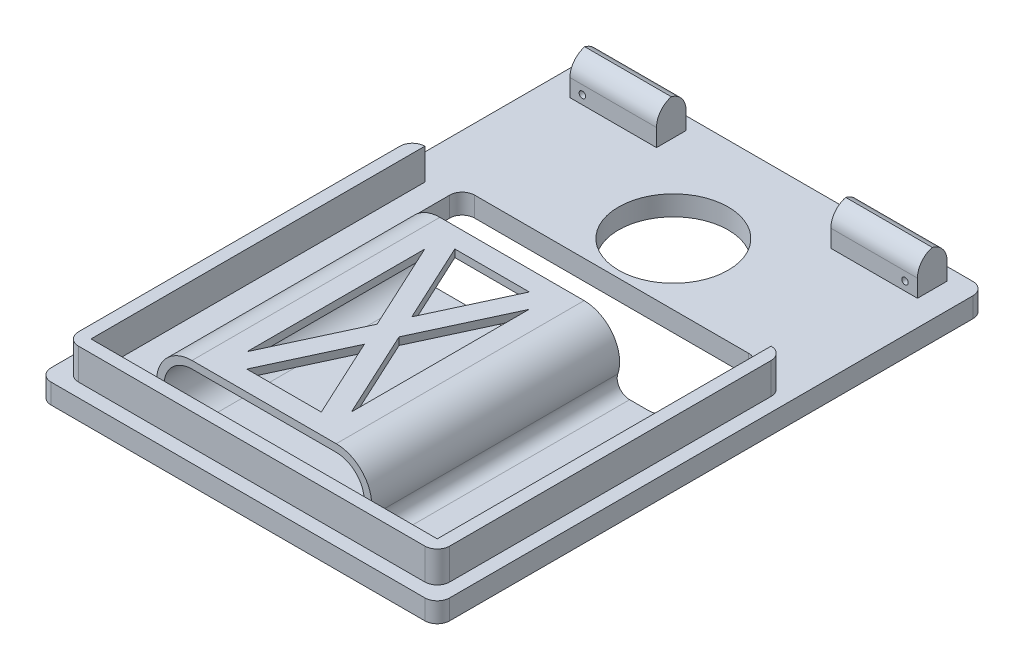
SolidWorks part; units mm, degrees
ref_plane "Front Plane" through (0, 0, 0) normal (0, 0, 1) x (1, 0, 0)
ref_plane "Top Plane" through (0, 0, 0) normal (0, 1, 0) x (1, 0, 0)
ref_plane "Right Plane" through (0, 0, 0) normal (1, 0, 0) x (0, 0, -1)
sketch "Sketch3" plane through (0, 0, 0) normal (0, 1, 0) x (1, 0, 0)
  line L0 (-75, 110) -> (75, 110)
  line L1 (-75, -105) -> (75, -105)
  line L2 (-75, -105) -> (-75, 105)
  line L4 (75, -105) -> (75, 105)
  line L5 (-75, -105) -> (75, 105) construction
  line L6 (-75, 105) -> (75, -105) construction
  line L7 (80, -105) -> (80, 105)
  line L8 (-75, -110) -> (75, -110)
  line L9 (-80, -105) -> (-80, 105)
  line L10 (-80, -110) -> (80, -110) construction
  line L11 (-80, -110) -> (-80, 110) construction
  line L12 (80, -110) -> (80, 110) construction
  line L13 (-80, 110) -> (80, 110) construction
  line L15 (-75, 105) -> (75, 105)
  line L19 (-75, 105) -> (75, 105) construction
  line L20 (-69.75, 104.9) -> (69.75, 104.9)
  line L21 (-69.75, 104.9) -> (-69.75, 93)
  line L22 (-69.75, 93) -> (69.75, 93)
  line L23 (69.75, 104.9) -> (69.75, 93)
  arc A0 (-75, -110) -> (-80, -105) centre (-75, -105) cw
  arc A1 (80, -105) -> (75, -110) centre (75, -105) cw
  arc A2 (75, 110) -> (80, 105) centre (75, 105) cw
  arc A3 (-75, 110) -> (-80, 105) centre (-75, 105) ccw
  point P0 (0, 0)
  point P5 (0, 93)
  dimension "D4" = 5
  dimension "D1" = 75
  dimension "D2" = 210
  dimension "D5" = 11.9
  dimension "D6" = 139.5
  dimension "D7" = 0.1
  dimension "D3" = 5
extrude "Boss-Extrude1" add sketch "Sketch3" along normal blind 8 contours L1 L4 L2 | L0 A3 L9 A0 L8 A1 L7 A2 L4 L1 L2 | L2 L4 | L23 L15 L21 L22 region at (0, 0, -107.2797) region at (0, 0, 5.5048) region at (0, 0, -98.95)
extrude "Boss-Extrude2" add sketch "Sketch3<7>" along normal blind 15 from surface contours L23 L15 L21 L22 region at (0, 0, -98.95) starting at face at (0, 8, 0)
sketch "Sketch3<7>" plane through (0, 0, 0) normal (0, 1, 0) x (1, 0, 0) same geometry as "Sketch3"
fillet "Fillet1" radius 8 2 edges at (0, 23, -93) (0, 23, -104.9)
sketch "Sketch4" plane through (0, 0, 0) normal (0, -1, 0) x (1, 0, 0)
  line L1 (-55, 0) -> (55, 0)
  line L2 (-60, -5) -> (-60, -35)
  line L3 (-55, -40) -> (55, -40)
  line L4 (60, -5) -> (60, -35)
  line L5 (-75, 110) -> (75, 110) construction
  line L6 (80, 105) -> (80, -105) construction
  line L7 (-75, -110) -> (75, -110) construction
  arc A0 (-55, 0) -> (-60, -5) centre (-55, -5) ccw
  arc A1 (-60, -35) -> (-55, -40) centre (-55, -35) ccw
  arc A2 (55, -40) -> (60, -35) centre (55, -35) ccw
  arc A3 (55, 0) -> (60, -5) centre (55, -5) cw
  point P4 (0, -40)
  dimension "D4" = 5
  dimension "D1" = 70
  dimension "D2" = 110
  dimension "D3" = 20
extrude "Cut-Extrude1" cut sketch "Sketch4" against normal up to next
sketch "Sketch5" plane through (0, 8, 0) normal (0, 1, 0) x (1, 0, 0)
  line L0 (75, -105) -> (75, 105) construction
  line L1 (-75, -105) -> (75, -105) construction
  line L2 (-75, -105) -> (-75, 105) construction
  line L3 (-75, 105) -> (75, 105) construction
  line L4 (75, 110) -> (-75, 110)
  line L5 (80, -105) -> (80, 105)
  line L6 (-75, -110) -> (75, -110)
  line L7 (-80, 105) -> (-80, -105)
  line L8 (75, 110) -> (-75, 110)
  line L9 (80, -105) -> (80, 105)
  line L10 (-75, -110) -> (75, -110)
  line L11 (-80, 105) -> (-80, -105)
  line L12 (69.75, 104.9) -> (-69.75, 104.9)
  line L13 (-69.75, 104.9) -> (-69.75, 93)
  line L14 (-69.75, 93) -> (69.75, 93)
  line L15 (69.75, 93) -> (69.75, 104.9)
  line L16 (69.75, 104.9) -> (-69.75, 104.9)
  line L17 (-69.75, 104.9) -> (-69.75, 93)
  line L18 (-69.75, 93) -> (69.75, 93)
  line L19 (69.75, 93) -> (69.75, 104.9)
  line L20 (75, -105) -> (75, 105)
  line L21 (-75, -105) -> (75, -105)
  line L22 (-75, -105) -> (-75, 105)
  line L23 (-75, 105) -> (75, 105)
  line L24 (-75, 35) -> (75, 35)
  line L25 (-69.5, 34.5) -> (-69.5, -99.5)
  line L26 (-69.5, -104.5) -> (69.5, -104.5)
  line L27 (-74.5, -99.5) -> (-74.5, 29.5)
  line L28 (-69.5, 34.5) -> (69.5, 34.5)
  line L29 (74.5, -99.5) -> (74.5, 29.5)
  line L30 (-69.5, -99.5) -> (69.5, -99.5)
  line L31 (69.5, -99.5) -> (69.5, 34.5)
  arc A0 (-74.5, 29.5) -> (-69.5, 34.5) centre (-69.5, 29.5) cw
  arc A1 (69.5, 34.5) -> (74.5, 29.5) centre (69.5, 29.5) cw
  arc A2 (69.5, -104.5) -> (74.5, -99.5) centre (69.5, -99.5) ccw
  arc A3 (-69.5, -104.5) -> (-74.5, -99.5) centre (-69.5, -99.5) cw
  arc A4 (80, 105) -> (75, 110) centre (75, 105) ccw
  arc A5 (75, -110) -> (80, -105) centre (75, -105) ccw
  arc A6 (-80, -105) -> (-75, -110) centre (-75, -105) ccw
  arc A7 (-75, 110) -> (-80, 105) centre (-75, 105) ccw
  arc A8 (80, 105) -> (75, 110) centre (75, 105) ccw
  arc A9 (75, -110) -> (80, -105) centre (75, -105) ccw
  arc A10 (-80, -105) -> (-75, -110) centre (-75, -105) ccw
  arc A11 (-75, 110) -> (-80, 105) centre (-75, 105) ccw
  point P26 (0, -104.5)
  point P42 (0, -99.5)
  dimension "D7" = 5
  dimension "D3" = 75
  dimension "D4" = 0.5
  dimension "D5" = 0.5
  dimension "D6" = 0.5
  dimension "D8" = 5
  dimension "D9" = 5
  dimension "D1" = 0
  dimension "D2" = 0
extrude "Boss-Extrude3" add sketch "Sketch5" along normal blind 12.5 contours A3 L26 A2 L29 A1 L31 L30 L25 A0 L27 region at (-71.5377, 8, 32.5)
sketch "Sketch6" plane through (0, 0, -104.9) normal (0, 0, -1) x (-1, 0, 0)
  line L0 (-69.75, 15) -> (-69.75, 8) construction
  line L1 (0, 0) -> (0, 22.7329) construction
  line L2 (-69.75, 22.7329) -> (69.75, 22.7329) construction
  circle A0 centre (-64.75, 11.5) radius 1.3
  circle A1 centre (64.75, 11.5) radius 1.3
  point P5 (-69.75, 11.5)
  dimension "D1" = 2.6
  dimension "D2" = 5
extrude "Cut-Extrude2" cut sketch "Sketch6" against normal up to next
sketch "Sketch8" plane through (0, 0, 99.5) normal (0, 0, -1) x (-1, 0, 0)
  line L0 (-28.95, 19.05) -> (28.95, 19.05) construction
  line L1 (-28.95, 30.1) -> (28.95, 30.1)
  line L2 (-28.95, 8) -> (28.95, 8)
  line L3 (69.5, 8) -> (-69.5, 8) construction
  line L4 (0, 19.05) -> (0, 0) construction
  line L5 (-28.95, 30.3) -> (28.95, 30.3)
  line L6 (-28.95, 7.8) -> (28.95, 7.8)
  line L7 (-28.95, 33.3) -> (28.95, 33.3)
  line L8 (-28.95, 4.8) -> (28.95, 4.8)
  line L9 (-37.9478, 8) -> (37.9478, 8)
  arc A0 (-28.95, 30.1) -> (-28.95, 8) centre (-28.95, 19.05) ccw
  arc A1 (28.95, 8) -> (28.95, 30.1) centre (28.95, 19.05) ccw
  arc A2 (28.95, 7.8) -> (28.95, 30.3) centre (28.95, 19.05) ccw
  arc A3 (-28.95, 30.3) -> (-28.95, 7.8) centre (-28.95, 19.05) ccw
  arc A4 (28.95, 4.8) -> (28.95, 33.3) centre (28.95, 19.05) ccw
  arc A5 (-28.95, 33.3) -> (-28.95, 4.8) centre (-28.95, 19.05) ccw
  point P2 (0, 19.05)
  line M6 (-69.5, 8) -> (69.5, 8)
  line M8 (69.5, 20.5) -> (-69.5, 20.5)
  dimension "D2" = 80
  dimension "D1" = 22.1
  dimension "D3" = 0.2
  dimension "D4" = 3
extrude "Boss-Extrude4" add sketch "Sketch8" along normal up to surface (99.5 mm away) contours L7 A5 A3 L5 A2 A4 M8 | L9 A4 A2 M8 | A5 A3 M8 M6 region at (41.6161, 21.372, 99.5) region at (39.5627, 13.5654, 99.5) region at (-39.5627, 13.5654, 99.5) up to face at (0, 4, 0)
fillet "Fillet2" radius 5 2 edges at (-37.9478, 8, 49.75) (37.9478, 8, 49.75)
sketch "Sketch9" plane through (0, 8, 0) normal (0, 1, 0) x (1, 0, 0)
  line L0 (69.75, 98.95) -> (-69.75, 98.95) construction
  line L1 (-35, 104.9) -> (35, 104.9)
  line L2 (-35, 104.9) -> (-35, 93)
  line L3 (-35, 93) -> (35, 93)
  line L4 (35, 104.9) -> (35, 93)
  line L5 (-35, 104.9) -> (35, 93) construction
  line L6 (-35, 93) -> (35, 104.9) construction
  line L7 (69.75, 93) -> (-69.75, 93) construction
  point P0 (0, 98.95)
  dimension "D1" = 70
extrude "Cut-Extrude3" cut sketch "Sketch9" along normal up to next
sketch "Sketch10" plane through (0, 33.3, 0) normal (0, 1, 0) x (1, 0, 0)
  line L0 (-20.95, -85.4223) -> (-4.4091, -49.75)
  line L1 (-4.4091, -49.75) -> (-20.95, -14.0777)
  line L2 (-14.95, -8) -> (0, -40.2413)
  line L3 (0, -40.2413) -> (14.95, -8)
  line L4 (28.95, 0) -> (-28.95, 0)
  line L5 (-28.95, 0) -> (-28.95, -99.5)
  line L6 (-28.95, -99.5) -> (28.95, -99.5)
  line L7 (28.95, -99.5) -> (28.95, 0)
  line L8 (28.95, 0) -> (-28.95, 0)
  line L9 (-28.95, 0) -> (-28.95, -99.5)
  line L10 (-28.95, -99.5) -> (28.95, -99.5)
  line L11 (28.95, -99.5) -> (28.95, 0)
  line L12 (0, -8) -> (0, -91.5) construction
  line L13 (20.95, -49.75) -> (-20.95, -49.75) construction
  line L14 (20.95, -85.4223) -> (4.4091, -49.75)
  line L15 (4.4091, -49.75) -> (20.95, -14.0777)
  line L16 (20.95, -8) -> (-20.95, -8)
  line L17 (-20.95, -8) -> (-20.95, -91.5)
  line L18 (-20.95, -91.5) -> (20.95, -91.5)
  line L19 (20.95, -91.5) -> (20.95, -8)
  line L20 (20.95, -8) -> (-20.95, -8)
  line L21 (-20.95, -8) -> (-20.95, -91.5)
  line L22 (-20.95, -91.5) -> (20.95, -91.5)
  line L23 (20.95, -91.5) -> (20.95, -8)
  line L24 (0, -59.2587) -> (14.95, -91.5)
  line L25 (-14.95, -91.5) -> (0, -59.2587)
  dimension "D3" = 8
  dimension "D4" = 6
  dimension "D1" = 0
  dimension "D2" = 8
extrude "Cut-Extrude4" cut sketch "Sketch10" against normal up to next contours L14 L23 L15 | L25 L22 L24 | L3 L20 L2 | L1 L21 L0 region at (-15.4364, 33.3, 49.75) region at (0, 33.3, 80.7529) region at (0, 33.3, 18.7471) region at (15.4364, 33.3, 49.75)
sketch "Sketch11" plane through (0, 0, 0) normal (0, -1, 0) x (1, 0, 0)
  circle A0 centre (0, -64.78) radius 22
  dimension "D1" = 44
extrude "Cut-Extrude5" cut sketch "Sketch11" against normal up to next
